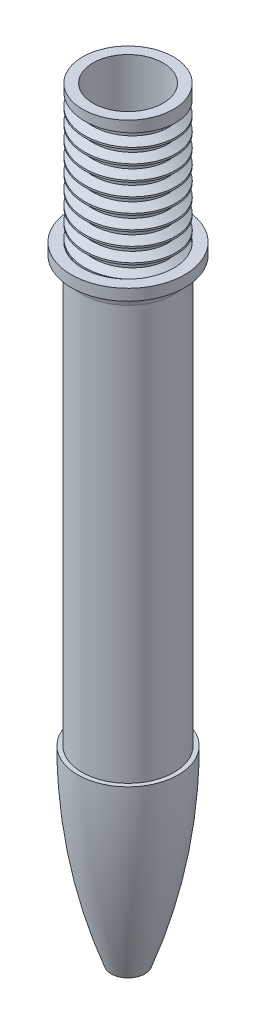
SolidWorks part; units mm, degrees
note: '?' marks a value the reader was unsure of.
material "PP Copolymer"
ref_plane "Front Plane" through (0, 0, 0) normal (0, 0, 1) x (1, 0, 0)
ref_plane "Top Plane" through (0, 0, 0) normal (0, 1, 0) x (1, 0, 0)
ref_plane "Right Plane" through (0, 0, 0) normal (1, 0, 0) x (0, 0, -1)
ref_axis "X-axis" through (-88.99, 0, 0) along (1, 0, 0)?
ref_axis "Y-axis" through (0, 55, 0) along (0, -1, 0)?
ref_axis "Z-axis" through (0, 0, -88.99) along (0, 0, 1)?
sketch "Sketch1" plane through (0, 0, 0) normal (0, 0, 1) x (1, 0, 0)
  line L0 (0, 0) -> (0, 67.85) construction
  line L1 (-4.04, 67.85) -> (-4.04, 55.61)
  line L2 (-4.04, 55.61) -> (-5.04, 55.61)
  line L3 (-5.04, 55.61) -> (-5.04, 54.61)
  line L4 (-5.04, 54.61) -> (-4.285, 54.61)
  line L5 (-4.285, 54.61) -> (-4.095, 53.6189)
  line L6 (-4.095, 53.6189) -> (-4.095, 16.82)
  line L7 (-1.5, 0) -> (-1.5, 5.6)
  line L8 (-4.095, 16.82) -> (-4.475, 16.82)
  line L9 (-1.5, 5.6) -> (-2.62, 5.6)
  line L12 (-2.62, 5.6) -> (-2.62, 10.6)
  line L13 (-2.62, 10.6) -> (-3.11, 10.6)
  line L14 (-3.11, 10.6) -> (-3.11, 67.85)
  line L15 (-3.11, 67.85) -> (-4.04, 67.85)
  arc A0 (-4.475, 16.82) -> (-1.5, 0) centre (44.5608, 16.82) ccw
  point P13 (-4.095, 35.2195)
  point P17 (-4.6625, 54.61)
  dimension "D11" = 3
  dimension "D1" = 67.85
  dimension "D2" = 8.08
  dimension "D3" = 10.08
  dimension "D4" = 8.57
  dimension "D5" = 8.19
  dimension "D6" = 8.95
  dimension "D7" = 12.24
  dimension "D8" = 1
  dimension "D9" = 169.147
  dimension "D10" = 37.79
  dimension "D12" = 5.6
  dimension "D13" = 1.12
  dimension "D14" = 0.93
  dimension "D15" = 5
revolve "Revolve1" add sketch "Sketch1" angle 360 about L0
thread "Thread1" start angle 0, offset 0.5, length 0, pitch 1.27, diameter 8.08
ref_plane "Plane1" through (-4.04, 67.35, 0) normal (0, 0, 1) x (-1, 0, 0)
sketch "Thread Profile1" plane through (-4.04, 67.35, 0) normal (0, 0, 1) x (-1, 0, 0)
  line L0 (0, 0) -> (0, 1.27) construction
  line L11 (0, 0) -> (0, 1.1112)
  line L12 (0, 1.1112) -> (-0.6874, 0.7144)
  line L13 (-0.6874, 0.7144) -> (-0.6874, 0.3969)
  line L15 (-0.6874, 0.3969) -> (0, 0)
  line L17 (-0.6874, 0.5556) -> (0, 0.5556) construction
  point P2 (0, 0)
  dimension "Pitch" = 1.27
  dimension "Profile_Angle" = 60
  dimension "Profile_Land" = 0.3175
  dimension "Profile_Height" = 0.6874
